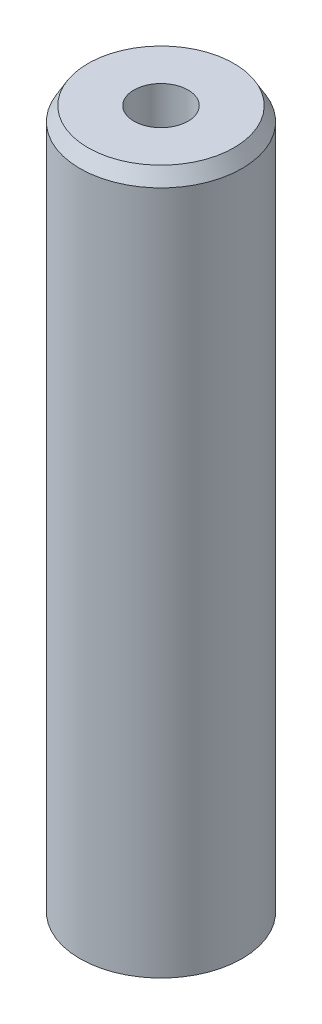
SolidWorks part; units mm, degrees
ref_plane "Front Plane" through (0, 0, 0) normal (0, 0, 1) x (1, 0, 0)
ref_plane "Top Plane" through (0, 0, 0) normal (0, 1, 0) x (1, 0, 0)
ref_plane "Right Plane" through (0, 0, 0) normal (1, 0, 0) x (0, 0, -1)
sketch "Sketch1" plane through (0, 0, 0) normal (0, 1, 0) x (1, 0, 0)
  circle A0 centre (0, 0) radius 5
  dimension "SHAFT_OD" = 10
extrude "Boss-Extrude1" add sketch "Sketch1" along normal blind 43.564
sketch "Sketch2" plane through (0, 0, 0) normal (0, 1, 0) x (1, 0, 0)
  circle A0 centre (0, 0) radius 1.6697
  dimension "BORE_D" = 3.3394
extrude "Cut-Extrude1" cut sketch "Sketch2" along normal through all
chamfer "Chamfer1" distance 0.862 angle 30 2 edges at (0, 43.564, 5) (0, 0, 5) first distance on face at (0, 43.564, 5) first distance on face at (0, 0, 1.6697)
